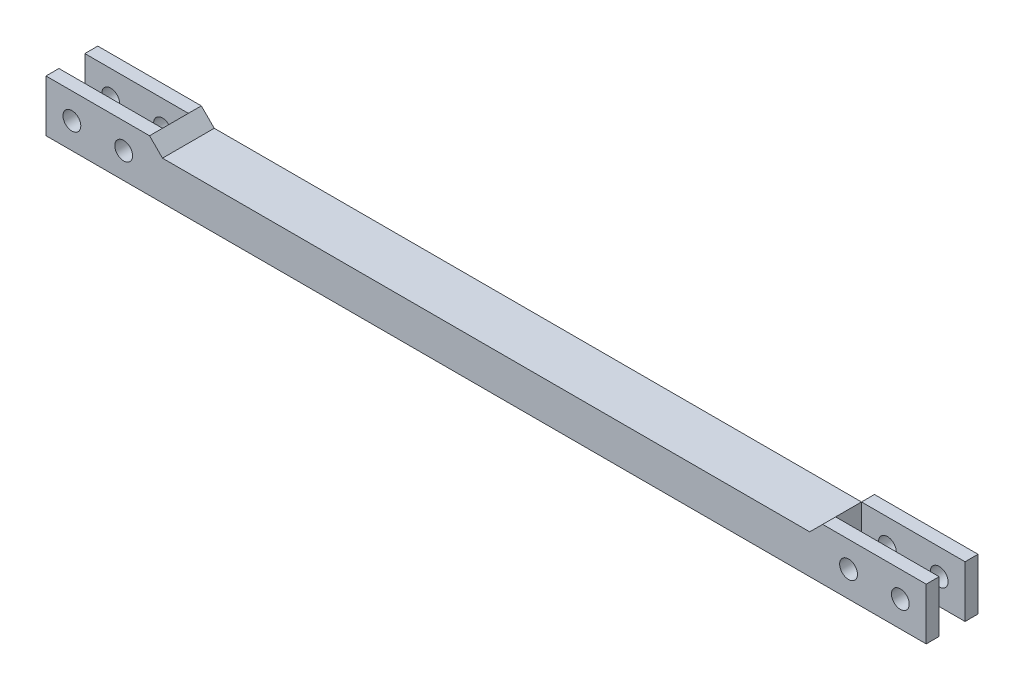
SolidWorks part; units mm, degrees
ref_plane "Front Plane" through (0, 0, 0) normal (0, 0, 1) x (1, 0, 0)
ref_plane "Top Plane" through (0, 0, 0) normal (0, 1, 0) x (1, 0, 0)
ref_plane "Right Plane" through (0, 0, 0) normal (1, 0, 0) x (0, 0, -1)
sketch "Sketch1" plane through (0, 0, 0) normal (0, 1, 0) x (1, 0, 0)
  line L0 (-107.95, 0) -> (107.95, 0)
  line L1 (107.95, 0) -> (107.95, 3.175)
  line L2 (107.95, 3.175) -> (82.55, 3.175)
  line L3 (82.55, 3.175) -> (82.55, 9.525)
  line L4 (82.55, 9.525) -> (107.95, 9.525)
  line L5 (107.95, 9.525) -> (107.95, 12.7)
  line L6 (107.95, 12.7) -> (-107.95, 12.7)
  line L7 (-107.95, 12.7) -> (-107.95, 9.525)
  line L8 (-107.95, 9.525) -> (-82.55, 9.525)
  line L9 (-82.55, 9.525) -> (-82.55, 3.175)
  line L10 (-82.55, 3.175) -> (-107.95, 3.175)
  line L11 (-107.95, 3.175) -> (-107.95, 0)
  point P3 (0, 0)
  point P4 (0, 0)
  dimension "D1" = 215.9
  dimension "D2" = 12.7
  dimension "D3" = 3.175
  dimension "D4" = 3.175
  dimension "D5" = 25.4
  dimension "D6" = 25.4
extrude "Boss-Extrude1" add sketch "Sketch1" along normal mid plane 12.7
sketch "Sketch2" plane through (0, 0, 0) normal (0, 0, 1) x (1, 0, 0)
  line L0 (-107.95, 6.35) -> (-107.95, -6.35) construction
  line L1 (107.95, 6.35) -> (107.95, -6.35) construction
  circle A0 centre (-101.6, 0) radius 2.1828
  circle A1 centre (-88.9, 0) radius 2.1828
  circle A2 centre (101.6, 0) radius 2.1828
  circle A3 centre (88.9, 0) radius 2.1828
  point P13 (0, 0)
  dimension "D5" = 4.3656
  dimension "D6" = 4.3656
  dimension "D7" = 4.3656
  dimension "D8" = 4.3656
  dimension "D1" = 6.35
  dimension "D2" = 12.7
  dimension "D3" = 6.35
  dimension "D4" = 12.7
extrude "Cut-Extrude1" cut sketch "Sketch2" against normal through all both and the other way through all
sketch "Sketch3" plane through (0, 0, 0) normal (0, 0, 1) x (1, 0, 0)
  line L0 (-82.55, 6.35) -> (-79.375, 3.175)
  line L1 (-107.95, 6.35) -> (107.95, 6.35) construction
  line L2 (-79.375, 3.175) -> (79.375, 3.175)
  line L3 (79.375, 3.175) -> (82.55, 6.35)
  line L4 (-107.95, 6.35) -> (-107.95, -6.35) construction
  line L5 (107.95, 6.35) -> (107.95, -6.35) construction
  line L6 (-82.55, 6.35) -> (82.55, 6.35)
  dimension "D1" = 25.4
  dimension "D2" = 25.4
  dimension "D3" = 3.175
  dimension "D4" = 45
  dimension "D5" = 45
extrude "Cut-Extrude2" cut sketch "Sketch3" against normal through all both and the other way through all
